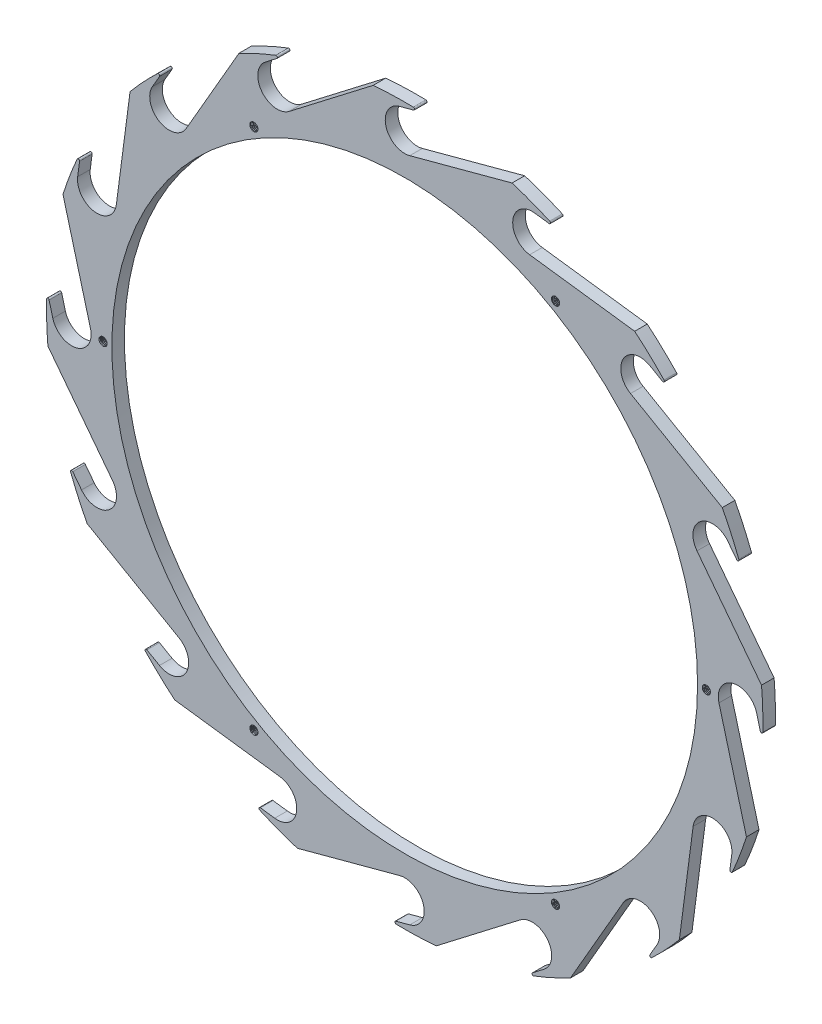
SolidWorks part; units mm, degrees
ref_plane "Piano frontale" through (0, 0, 0) normal (0, 0, 1) x (1, 0, 0)
ref_plane "Piano superiore" through (0, 0, 0) normal (0, 1, 0) x (1, 0, 0)
ref_plane "Piano destro" through (0, 0, 0) normal (1, 0, 0) x (0, 0, -1)
sketch "Schizzo1" plane through (0, 0, 0) normal (0, 0, 1) x (1, 0, 0)
  line L1 (4.022, -279.9691) -> (-13.5097, -284.6796)
  line L33 (-4.022, -250.0309) -> (-85.4138, -271.8998)
  line L78 (-99.3985, -229.4593) -> (-182.9636, -218.5162)
  line L80 (-103.4237, -260.1969) -> (-121.4235, -257.8397)
  line L82 (-179.6425, -173.9546) -> (-252.6588, -131.8655)
  line L84 (-195.1241, -200.812) -> (-210.8517, -191.7461)
  line L86 (-232.5376, -91.9669) -> (-283.8891, -25.1395)
  line L89 (-257.1186, -110.8554) -> (-268.1796, -96.4608)
  line L90 (-250.0309, 4.022) -> (-271.8998, 85.4138)
  line L96 (-279.9691, -4.022) -> (-284.6796, 13.5097)
  line L97 (-229.4593, 99.3985) -> (-218.5162, 182.9636)
  line L98 (-260.1969, 103.4237) -> (-257.8397, 121.4235)
  line L99 (-173.9546, 179.6425) -> (-131.8655, 252.6588)
  line L100 (-200.812, 195.1241) -> (-191.7461, 210.8517)
  line L101 (-91.9669, 232.5376) -> (-25.1395, 283.8891)
  line L102 (-110.8554, 257.1186) -> (-96.4608, 268.1796)
  line L103 (4.022, 250.0309) -> (85.4138, 271.8998)
  line L104 (-4.022, 279.9691) -> (13.5097, 284.6796)
  line L105 (99.3985, 229.4593) -> (182.9636, 218.5162)
  line L106 (103.4237, 260.1969) -> (121.4235, 257.8397)
  line L107 (179.6425, 173.9546) -> (252.6588, 131.8655)
  line L108 (195.1241, 200.812) -> (210.8517, 191.7461)
  line L109 (232.5376, 91.9669) -> (283.8891, 25.1395)
  line L110 (257.1186, 110.8554) -> (268.1796, 96.4608)
  line L111 (250.0309, -4.022) -> (271.8998, -85.4138)
  line L112 (279.9691, 4.022) -> (284.6796, -13.5097)
  line L113 (229.4593, -99.3985) -> (218.5162, -182.9636)
  line L114 (260.1969, -103.4237) -> (257.8397, -121.4235)
  line L115 (173.9546, -179.6425) -> (131.8655, -252.6588)
  line L116 (200.812, -195.1241) -> (191.7461, -210.8517)
  line L117 (91.9669, -232.5376) -> (25.1395, -283.8891)
  line L118 (110.8554, -257.1186) -> (96.4608, -268.1796)
  line L119 (0, 0) -> (-4.022, -250.0309) construction
  line L120 (0, 0) -> (-99.3985, -229.4593) construction
  circle A2 centre (0, 0) radius 233
  arc A4 (4.022, -279.9691) -> (-4.022, -250.0309) centre (0, -265) ccw
  arc A20 (-210.8517, -191.7461) -> (-182.9636, -218.5162) centre (0, 0) ccw
  arc A21 (-103.4237, -260.1969) -> (-99.3985, -229.4593) centre (-101.4111, -244.8281) ccw
  arc A22 (-195.1241, -200.812) -> (-179.6425, -173.9546) centre (-187.3833, -187.3833) ccw
  arc A23 (-257.1186, -110.8554) -> (-232.5376, -91.9669) centre (-244.8281, -101.4111) ccw
  arc A24 (-279.9691, -4.022) -> (-250.0309, 4.022) centre (-265, 0) ccw
  arc A25 (-260.1969, 103.4237) -> (-229.4593, 99.3985) centre (-244.8281, 101.4111) ccw
  arc A26 (-200.812, 195.1241) -> (-173.9546, 179.6425) centre (-187.3833, 187.3833) ccw
  arc A27 (-110.8554, 257.1186) -> (-91.9669, 232.5376) centre (-101.4111, 244.8281) ccw
  arc A28 (-4.022, 279.9691) -> (4.022, 250.0309) centre (0, 265) ccw
  arc A29 (103.4237, 260.1969) -> (99.3985, 229.4593) centre (101.4111, 244.8281) ccw
  arc A30 (195.1241, 200.812) -> (179.6425, 173.9546) centre (187.3833, 187.3833) ccw
  arc A31 (257.1186, 110.8554) -> (232.5376, 91.9669) centre (244.8281, 101.4111) ccw
  arc A32 (279.9691, 4.022) -> (250.0309, -4.022) centre (265, 0) ccw
  arc A33 (260.1969, -103.4237) -> (229.4593, -99.3985) centre (244.8281, -101.4111) ccw
  arc A34 (200.812, -195.1241) -> (173.9546, -179.6425) centre (187.3833, -187.3833) ccw
  arc A35 (110.8554, -257.1186) -> (91.9669, -232.5376) centre (101.4111, -244.8281) ccw
  arc A36 (-121.4235, -257.8397) -> (-85.4138, -271.8998) centre (0, 0) ccw
  arc A37 (-13.5097, -284.6796) -> (25.1395, -283.8891) centre (0, 0) ccw
  arc A38 (96.4608, -268.1796) -> (131.8655, -252.6588) centre (0, 0) ccw
  arc A39 (191.7461, -210.8517) -> (218.5162, -182.9636) centre (0, 0) ccw
  arc A40 (257.8397, -121.4235) -> (271.8998, -85.4138) centre (0, 0) ccw
  arc A41 (284.6796, -13.5097) -> (283.8891, 25.1395) centre (0, 0) ccw
  arc A42 (210.8517, 191.7461) -> (182.9636, 218.5162) centre (0, 0) ccw
  arc A43 (268.1796, 96.4608) -> (252.6588, 131.8655) centre (0, 0) ccw
  arc A44 (13.5097, 284.6796) -> (-25.1395, 283.8891) centre (0, 0) ccw
  arc A45 (121.4235, 257.8397) -> (85.4138, 271.8998) centre (0, 0) ccw
  arc A46 (-96.4608, 268.1796) -> (-131.8655, 252.6588) centre (0, 0) ccw
  arc A47 (-191.7461, 210.8517) -> (-218.5162, 182.9636) centre (0, 0) ccw
  arc A48 (-268.1796, -96.4608) -> (-252.6588, -131.8655) centre (0, 0) ccw
  arc A49 (-257.8397, 121.4235) -> (-271.8998, 85.4138) centre (0, 0) ccw
  arc A50 (-284.6796, 13.5097) -> (-283.8891, -25.1395) centre (0, 0) ccw
  dimension "D1" = 570
  dimension "D2" = 16
  dimension "D3" = 31
  dimension "D4" = 466
  dimension "D5" = 22.5
extrude "Estrusione-Estrusione1" add sketch "Schizzo1" along normal blind 10
fillet "Raccordo2" radius 1 16 edges at (121.4235, 257.8397, 5) (284.6796, -13.5097, 5) (257.8397, -121.4235, 5) (191.7461, -210.8517, 5) (96.4608, -268.1796, 5) (-13.5097, -284.6796, 5) (-121.4235, -257.8397, 5) (-268.1796, -96.4608, 5) (-210.8517, -191.7461, 5) (-284.6796, 13.5097, 5) (-257.8397, 121.4235, 5) (-191.7461, 210.8517, 5) (-96.4608, 268.1796, 5) (13.5097, 284.6796, 5) (268.1796, 96.4608, 5) (210.8517, 191.7461, 5)
sketch "Schizzo2" plane through (0, 0, 10) normal (0, 0, 1) x (1, 0, 0)
  circle A0 centre (-240, 0) radius 3.25
  dimension "D3" = 6.5
  dimension "D1" = 240
  dimension "D2" = 0
extrude "Taglio-Estrusione1" cut sketch "Schizzo2" against normal up to surface (10 mm away) up to face at (0, 0, 0)
thread "Filettatura1" pitch 1 method cut profile "Profilo filettatura1" start angle 0, offset 0, length 0, pitch 1, diameter 6.5
ref_plane "Piano1" through (-243.25, 0, 10) normal (0, -1, 0) x (-1, 0, 0)
sketch "Profilo filettatura1" plane through (-243.25, 0, 10) normal (0, -1, 0) x (-1, 0, 0)
  line L0 (0, 0) -> (0, 1) construction
  line L1 (0, 0) -> (0.5413, 0.3125)
  line L2 (0.5413, 0.3125) -> (0.5413, 0.4375)
  line L3 (0.5413, 0.4375) -> (0, 0.75)
  line L4 (0.5413, 0.375) -> (0, 0.375) construction
  line L11 (0, 0) -> (0, 0.75)
  point P2 (0, 0)
  dimension "Pitch" = 1
  dimension "Profile_Angle" = 60
  dimension "Profile_Land" = 0.125
  dimension "Profile_Height" = 0.5413
pattern_circular "RipetizioneCircolare1" count 6 over 360 about axis through (0, 0, 10) along (0, 0, 1) of "Filettatura1", "Taglio-Estrusione1"
